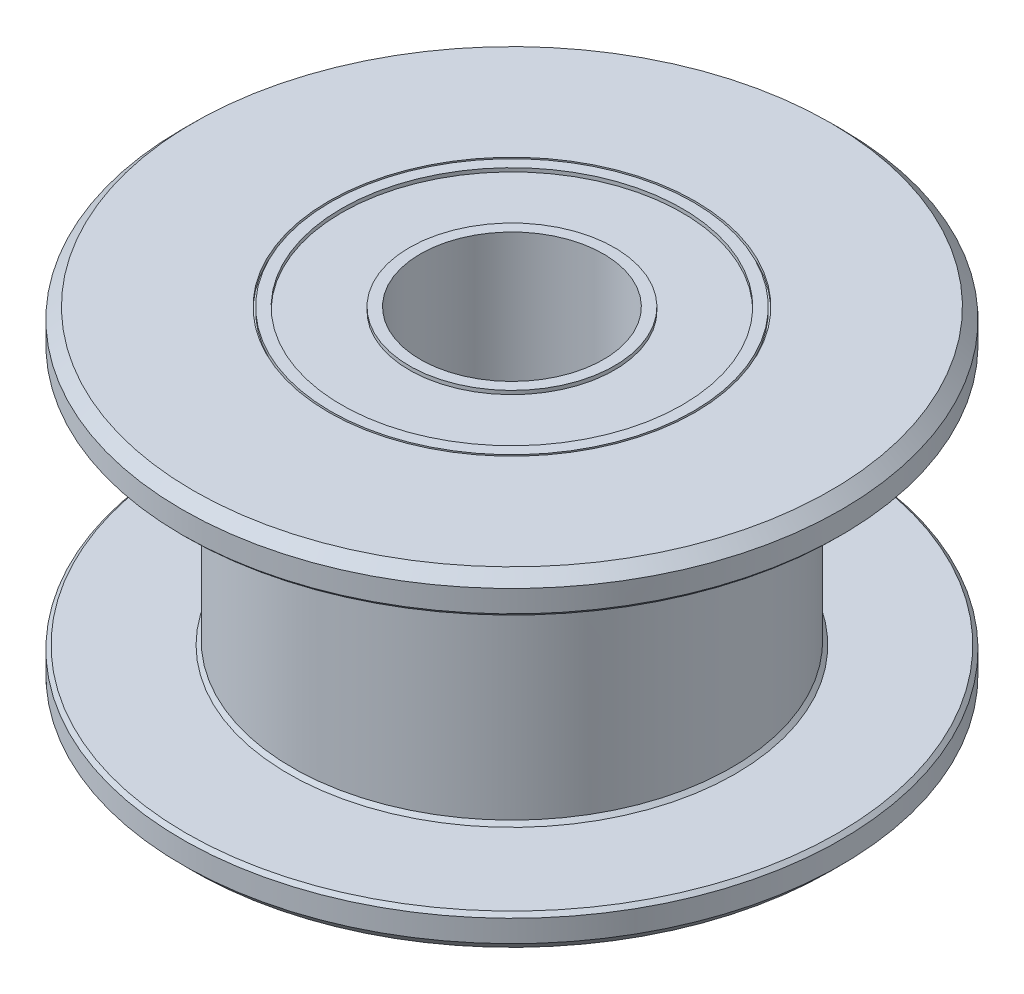
SolidWorks part; units mm, degrees
ref_plane "Alzado" through (0, 0, 0) normal (0, 0, 1) x (1, 0, 0)
ref_plane "Planta" through (0, 0, 0) normal (0, 1, 0) x (1, 0, 0)
ref_plane "Vista lateral" through (0, 0, 0) normal (1, 0, 0) x (0, 0, -1)
sketch "Croquis1" plane through (0, 0, 0) normal (0, 0, 1) x (1, 0, 0)
  line L0 (6.5, 4.5) -> (2.5, 4.5)
  line L1 (2.5, 4.5) -> (2.5, 4.4)
  line L2 (-2.5, 4.5) -> (-2.5, -37.0697) construction
  line L3 (2.5, 4.4) -> (2.45, 4.4)
  line L4 (6.5, 4.5) -> (6.5, 3.5)
  line L5 (6.5, 3.5) -> (3.5, 3.5)
  line L6 (3.5, 3.5) -> (3.5, -3.5)
  line L7 (3.5, -3.5) -> (6.5, -3.5)
  line L8 (6.5, -4.5) -> (1.7, -4.5)
  line L9 (6.5, -3.5) -> (6.5, -4.5)
  line L10 (0, 0.05) -> (0, -4.4)
  line L11 (0, -4.4) -> (1.7, -4.4)
  line L12 (1.7, -4.4) -> (1.7, -4.5)
  line L13 (2.15, 4.4) -> (0.3, 4.4)
  line L15 (0, 0.05) -> (0, 4.5)
  line L16 (0, 4.5) -> (0.3, 4.5)
  line L17 (0.3, 4.4) -> (0.3, 4.5)
  line L19 (2.45, 4.4) -> (2.45, 4.5)
  line L20 (2.45, 4.5) -> (2.15, 4.5)
  line L21 (2.15, 4.4) -> (2.15, 4.5)
  line L22 (3.5, 0) -> (0, 0) construction
  point P0 (6.5, 4)
  dimension "D1" = 9
  dimension "D2" = 6
  dimension "D3" = 9
  dimension "D4" = 1
  dimension "D5" = 1
  dimension "D6" = 9
  dimension "D7" = 0.1
  dimension "D8" = 0.1
  dimension "D9" = 2.5
  dimension "D10" = 4
  dimension "D11" = 0.3
  dimension "D12" = 0.3
  dimension "D13" = 0.05
  dimension "D14" = 1.7
revolve "Revolución3" add sketch "Croquis1" angle 360 about L2
chamfer "Chaflán3" distance 0.3 angle 45 2 edges at (-11.5, -4.5, 0) (-11.5, 4.5, 0)
chamfer "Chaflán4" distance 0.1 angle 45 3 edges at (-11.5, -3.5, 0) (-8.5, -3.5, 0) (-11.5, 3.5, 0)
ref_axis "Axis1" through (-2.5, -4.4, 0) along (0, 1, 0)
sketch "Sketch1" plane through (0, 4.5, 0) normal (0, 1, 0) x (1, 0, 0)
  circle A0 centre (-2.5, 0) radius 10.2735
extrude "Cut-Extrude1" [suppressed] cut sketch "Sketch1" against normal up to surface (1 mm away)
